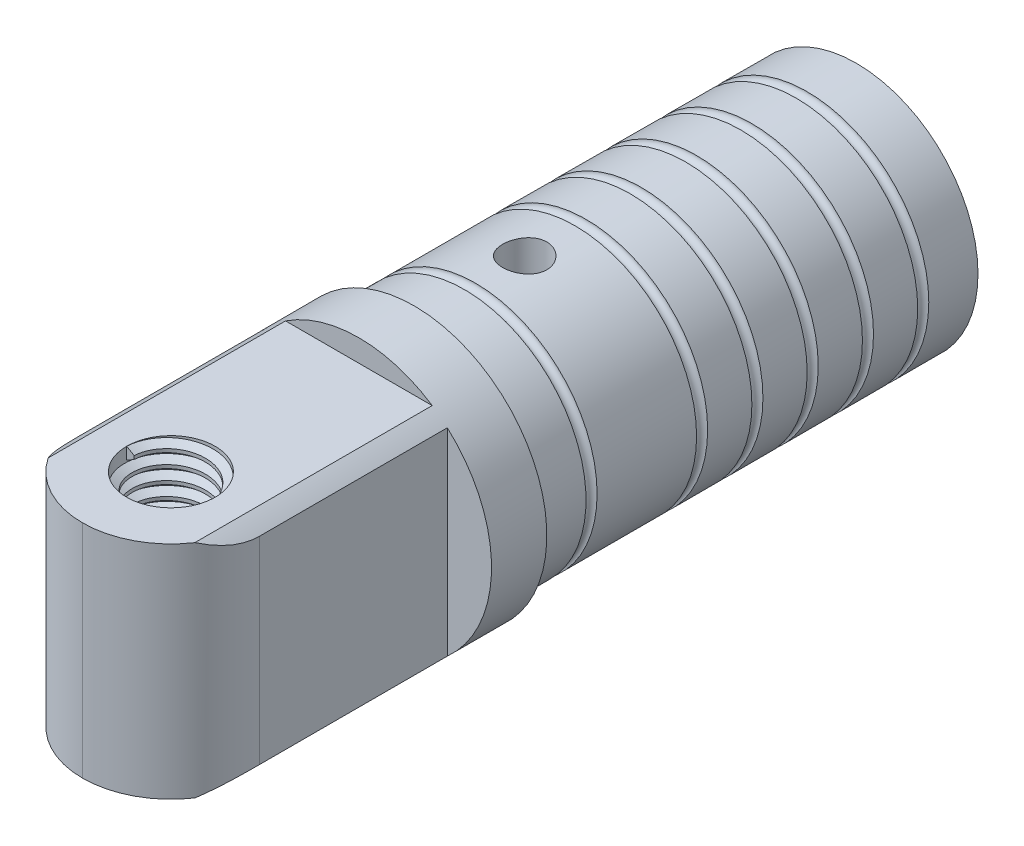
SolidWorks part; units mm, degrees
material "7075-T6 (SN)"
ref_plane "Ön Düzlem" through (0, 0, 0) normal (0, 0, 1) x (1, 0, 0)
ref_plane "Üst Düzlem" through (0, 0, 0) normal (0, 1, 0) x (1, 0, 0)
ref_plane "Sağ Düzlem" through (0, 0, 0) normal (1, 0, 0) x (0, 0, -1)
sketch "Çizim1" plane through (0, 0, 0) normal (0, 0, 1) x (1, 0, 0)
  line L0 (13, 0) -> (-13, 0) construction
  line L1 (0, 10) -> (0, -10) construction
  line L2 (8, 10) -> (-8, 10)
  line L3 (8, -10) -> (-8, -10)
  line L4 (-8, -10) -> (-8, 10)
  line L5 (8, -10) -> (8, 10)
  circle A0 centre (0, 0) radius 13 construction
  point P6 (0, 0)
  point P9 (0, 0)
  point P12 (0, 10)
  point P15 (0, -10)
  dimension "D1" = 26
  dimension "D2" = 20
  dimension "D3" = 16
extrude "Yükseklik-Ekstrüzyon3" add sketch "Çizim1" along normal blind 25
sketch "Çizim3" plane through (0, 0, 0) normal (0, 0, -1) x (-1, 0, 0)
  circle A0 centre (0, 0) radius 12
extrude "Yükseklik-Ekstrüzyon4" add sketch "Çizim3" along normal blind 5
sketch "Çizim4" plane through (0, 0, -5) normal (0, 0, -1) x (-1, 0, 0)
  circle A0 centre (0, 0) radius 11
  circle A1 centre (0, 0) radius 8
  dimension "D1" = 22
  dimension "D2" = 3
extrude "Yükseklik-Ekstrüzyon5" add sketch "Çizim4" along normal blind 30
fillet "Fillet1" radius 8 2 edges at (8, 0, 25) (-8, 0, 25)
sketch "Sketch1" plane through (0, 10, 0) normal (0, 1, 0) x (1, 0, 0)
  circle A0 centre (0, -17) radius 4
extrude "Cut-Extrude1" cut sketch "Sketch1" against normal blind 31 contours A0
sketch "Çizim6" plane through (0, 0, 0) normal (0, 0, 1) x (1, 0, 0)
  circle A0 centre (0, 0) radius 18.1172
  circle A1 centre (0, 0) radius 12
extrude "Kes-Ekstrüzyon2" cut sketch "Çizim6" along normal blind 100
sketch "Çizim7" plane through (0, 0, -35) normal (0, 0, -1) x (-1, 0, 0)
  circle A0 centre (0, 0) radius 8 construction
  circle A1 centre (0, 0) radius 11
  circle A2 centre (0, 0) radius 11
  circle A3 centre (0, 0) radius 8
  dimension "D1" = 0
extrude "Yükseklik-Ekstrüzyon6" add sketch "Çizim7" along normal blind 10
sketch "Sketch2" plane through (0, 0, 0) normal (0, 1, 0) x (1, 0, 0)
  line L0 (-11, 45.0481) -> (-11, 5.0481) construction
  line L1 (12, 5.0481) -> (-12, 5.0481) construction
  line L2 (-11, 10.0481) -> (11, 10.0481) construction
  line L3 (-11, 20.0481) -> (11, 20.0481) construction
  line L4 (-11, 25.0481) -> (11, 25.0481) construction
  line L5 (-11, 30.0481) -> (11, 30.0481) construction
  line L6 (-11, 35.0481) -> (11, 35.0481) construction
  line L7 (-11, 40.0481) -> (11, 40.0481) construction
  line L8 (0, 45.0481) -> (0, 5.0481) construction
  circle A0 centre (-11, 10.0481) radius 0.5
  circle A1 centre (-11, 20.0481) radius 0.5
  circle A2 centre (-11, 25.0481) radius 0.5
  circle A3 centre (-11, 30.0481) radius 0.5
  circle A4 centre (-11, 35.0481) radius 0.5
  circle A5 centre (-11, 40.0481) radius 0.5
  dimension "D6" = 1
  dimension "D7" = 1
  dimension "D8" = 1
  dimension "D9" = 1
  dimension "D10" = 1
  dimension "D11" = 1
  dimension "D1" = 5
  dimension "D2" = 10
  dimension "D3" = 10
  dimension "D4" = 5
  dimension "D5" = 5
revolve "Cut-Revolve1" cut sketch "Sketch2" angle 360 about L8
sketch "Sketch3" plane through (0, 0, 0) normal (0, 1, 0) x (1, 0, 0)
  line L0 (0, 5) -> (0, 15) construction
  line L1 (12, 5) -> (-12, 5) construction
  circle A0 centre (0, 15) radius 2
  dimension "D2" = 4
  dimension "D1" = 10
extrude "Cut-Extrude2" cut sketch "Sketch3" against normal blind 13 and the other way blind 13
thread "Thread1" pitch 1.25 method extrude profile "Thread Profile1" start angle 0, offset 0, length 0, pitch 1.25, diameter 8
ref_plane "Plane1" through (-4, 10, 17) normal (0, 0, 1) x (-1, 0, 0)
sketch "Thread Profile1" plane through (-4, 10, 17) normal (0, 0, 1) x (-1, 0, 0)
  line L0 (0, 0) -> (0, 1.25) construction
  line L11 (0, 0) -> (0, 1.0937)
  line L12 (0, 1.0937) -> (-0.6766, 0.7031)
  line L13 (-0.6766, 0.7031) -> (-0.6766, 0.3906)
  line L15 (-0.6766, 0.3906) -> (0, 0)
  line L17 (-0.6766, 0.5469) -> (0, 0.5469) construction
  point P2 (0, 0)
  dimension "Pitch" = 1.25
  dimension "Profile_Angle" = 60
  dimension "Profile_Land" = 0.3125
  dimension "Profile_Height" = 0.6766
